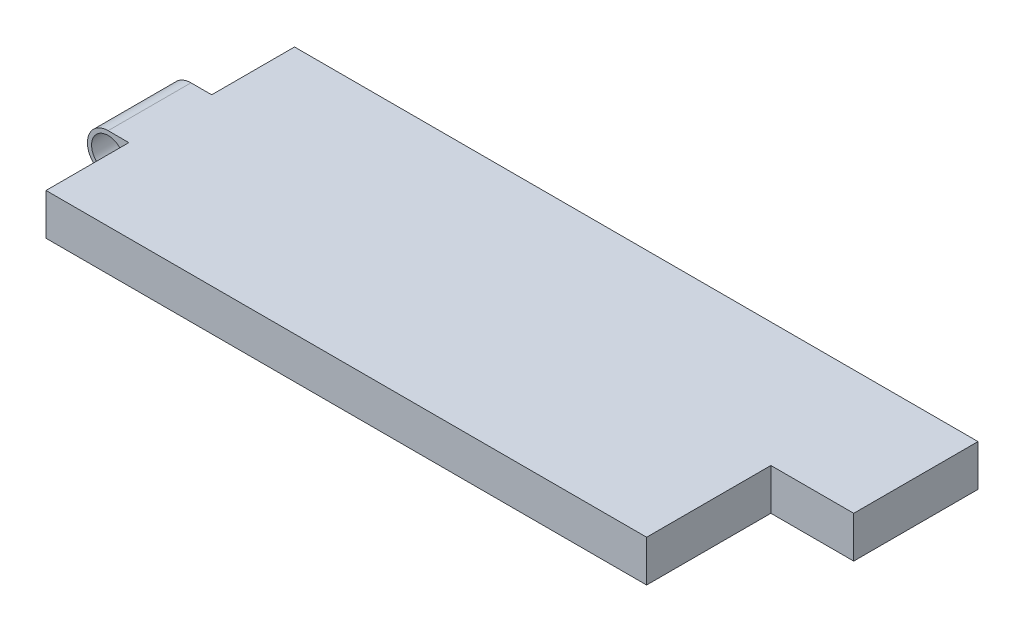
SolidWorks part; units mm, degrees
ref_plane "Plan de face" through (0, 0, 0) normal (0, 0, 1) x (1, 0, 0)
ref_plane "Plan de dessus" through (0, 0, 0) normal (0, 1, 0) x (1, 0, 0)
ref_plane "Plan de droite" through (0, 0, 0) normal (1, 0, 0) x (0, 0, -1)
sketch "Esquisse1" plane through (0, 0, 0) normal (0, 0, 1) x (1, 0, 0)
  line L0 (-80, 33.1442) -> (-80, -29.1403) construction
  line L5 (82.5, 15) -> (-82.5, -15) construction
  line L6 (82.5, -15) -> (-82.5, 15) construction
  line L7 (-88.7967, 0) -> (66.0295, 0) construction
  line L8 (-80, 2.5) -> (0, 2.5)
  line L9 (0, 2.5) -> (0, -2.5)
  line L10 (0, -2.5) -> (-80, -2.5)
  circle A0 centre (-80, 0) radius 2
  arc A1 (-80, 2.5) -> (-80, -2.5) centre (-80, 0) ccw
  point P0 (0, 0)
  dimension "D4" = 4
  dimension "D1" = 165
  dimension "D2" = 30
  dimension "D3" = 80
extrude "BASE" add sketch "Esquisse1" along normal blind 5 and the other way blind 5
sketch "Esquisse2" plane through (0, 0, 5) normal (0, 0, 1) x (1, 0, 0)
  line L0 (-77.5, 2.5) -> (-77.5, -2.5)
  line L1 (0, 2.5) -> (-80, 2.5) construction
  line L2 (-80, -2.5) -> (0, -2.5) construction
  line L3 (-77.5, -2.5) -> (0, -2.5)
  line L4 (0, -2.5) -> (0, 2.5)
  line L5 (0, 2.5) -> (-77.5, 2.5)
  dimension "D1" = 77.5
extrude "Boss.-Extru.2" add sketch "Esquisse2" along normal blind 10
sketch "Esquisse3" plane through (0, 0, -5) normal (0, 0, -1) x (-1, 0, 0)
  line L0 (0, 2.5) -> (0, -2.5)
  line L1 (0, -2.5) -> (77.5, -2.5)
  line L2 (80, -2.5) -> (0, -2.5) construction
  line L3 (77.5, -2.5) -> (77.5, 2.5)
  line L4 (0, 2.5) -> (80, 2.5) construction
  line L5 (77.5, 2.5) -> (0, 2.5)
  dimension "D1" = 77.5
extrude "Boss.-Extru.3" add sketch "Esquisse3" along normal blind 10
sketch "Esquisse4" plane through (0, 2.5, 0) normal (0, 1, 0) x (1, 0, 0)
  line L0 (0, 15) -> (5, 15)
  line L1 (5, 15) -> (5, 0)
  line L2 (5, 0) -> (0, 0)
  line L4 (0, 15) -> (0, 0)
  dimension "D1" = 5
extrude "Boss.-Extru.4" add sketch "Esquisse4" against normal blind 5
sketch "Esquisse5" plane through (0, 2.5, 0) normal (0, 1, 0) x (1, 0, 0)
  line L0 (0, 0) -> (-5, 0)
  line L1 (-5, 0) -> (-5, -15)
  line L2 (0, -15) -> (-77.5, -15) construction
  line L3 (-5, -15) -> (0, -15)
  line L4 (0, -15) -> (0, 0)
  dimension "D1" = 5
extrude "Enlèv. mat.-Extru.1" cut sketch "Esquisse5" against normal blind 5
